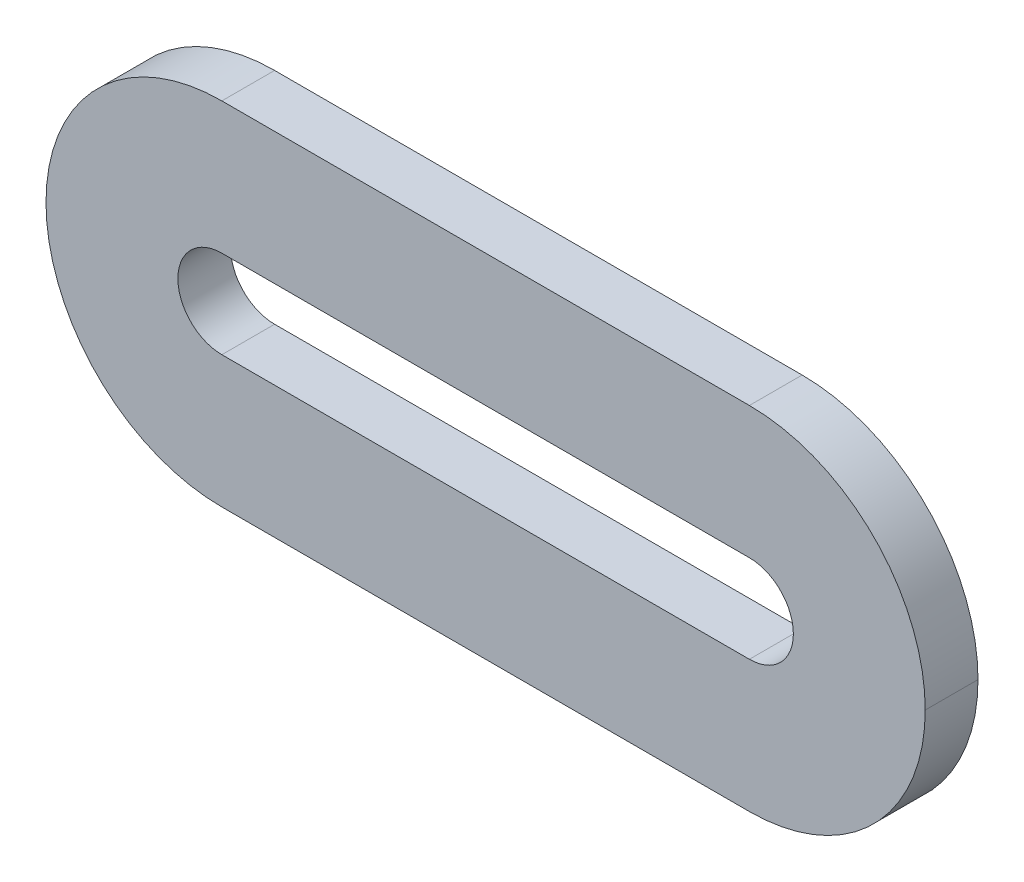
SolidWorks part; units mm, degrees
ref_plane "Front Plane" through (0, 0, 0) normal (0, 0, 1) x (1, 0, 0)
ref_plane "Top Plane" through (0, 0, 0) normal (0, 1, 0) x (1, 0, 0)
ref_plane "Right Plane" through (0, 0, 0) normal (1, 0, 0) x (0, 0, -1)
sketch "Sketch2" plane through (0, 0, 0) normal (0, 0, 1) x (1, 0, 0)
  line L0 (-15, 0) -> (15, 0) construction
  line L1 (-25, -10) -> (25, -10)
  line L2 (-25, -10) -> (-25, 10)
  line L3 (-25, 10) -> (25, 10)
  line L4 (25, -10) -> (25, 10)
  line L5 (-25, -10) -> (25, 10) construction
  line L6 (-25, 10) -> (25, -10) construction
  line L7 (-15, 2.5) -> (15, 2.5)
  line L8 (-15, -2.5) -> (15, -2.5)
  circle A0 centre (0, 0) radius 2.5 construction
  arc A1 (-15, 2.5) -> (-15, -2.5) centre (-15, 0) ccw
  arc A2 (15, -2.5) -> (15, 2.5) centre (15, 0) ccw
  point P0 (0, 0)
  point P10 (0, 0)
  dimension "D3" = 5
  dimension "D1" = 20
  dimension "D2" = 50
  dimension "D4" = 30
extrude "Boss-Extrude1" add sketch "Sketch2" along normal blind 3
fillet "Fillet1" radius 10 4 edges at (25, -10, 1.5) (-25, -10, 1.5) (-25, 10, 1.5) (25, 10, 1.5)
ref_plane "Plane1" through (0, 0, 0) normal (1, 0, 0) x (0, 0, -1)
